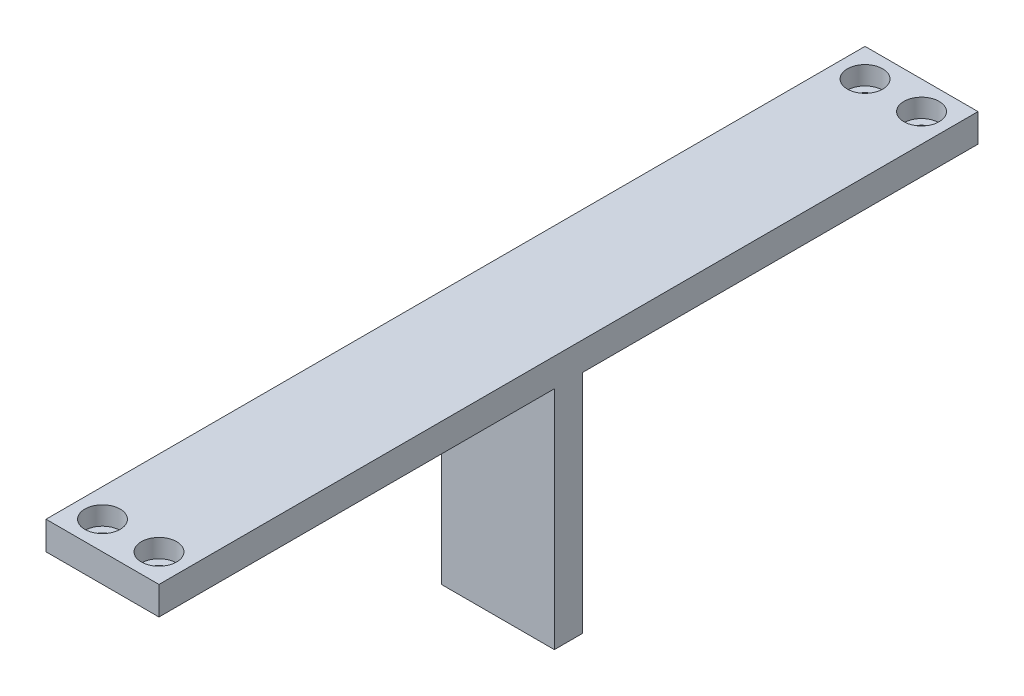
SolidWorks part; units mm, degrees
material "6061 Alloy"
ref_plane "Front Plane" through (0, 0, 0) normal (0, 0, 1) x (1, 0, 0)
ref_plane "Top Plane" through (0, 0, 0) normal (0, 1, 0) x (1, 0, 0)
ref_plane "Right Plane" through (0, 0, 0) normal (1, 0, 0) x (0, 0, -1)
sketch "Sketch1" plane through (0, 0, 0) normal (0, 1, 0) x (1, 0, 0)
  line L1 (-12.7, -92.075) -> (12.7, -92.075)
  line L2 (-12.7, -92.075) -> (-12.7, 92.075)
  line L3 (-12.7, 92.075) -> (12.7, 92.075)
  line L4 (12.7, -92.075) -> (12.7, 92.075)
  line L5 (-12.7, -92.075) -> (12.7, 92.075) construction
  line L6 (-12.7, 92.075) -> (12.7, -92.075) construction
  point P0 (0, 0)
  dimension "D1" = 184.15
  dimension "D2" = 25.4
extrude "Boss-Extrude1" add sketch "Sketch1" along normal blind 6.35
sketch "Sketch2" plane through (0, 0, 0) normal (0, -1, 0) x (-1, 0, 0)
  line L0 (-12.7, -92.075) -> (-12.7, 92.075) construction
  line L1 (12.7, 3.175) -> (-12.7, 3.175)
  line L2 (12.7, 3.175) -> (12.7, -3.175)
  line L3 (12.7, -3.175) -> (-12.7, -3.175)
  line L4 (-12.7, 3.175) -> (-12.7, -3.175)
  line L5 (12.7, 3.175) -> (-12.7, -3.175) construction
  line L6 (12.7, -3.175) -> (-12.7, 3.175) construction
  point P0 (0, 0)
  dimension "D1" = 6.35
extrude "Boss-Extrude2" add sketch "Sketch2" along normal blind 50.8
hole_wizard "CBORE for #8 Socket Head Cap Screw1" positions "Sketch4" profile "Sketch5" counterbore size "#8" standard "ANSI Inch" end condition up to next
sketch "Sketch4" plane through (0, 6.35, 0) normal (0, 1, 0) x (1, 0, 0)
  line L0 (-12.7, 92.075) -> (-12.7, -92.075) construction
  line L1 (-12.7, -92.075) -> (12.7, -92.075) construction
  line L2 (12.7, 92.075) -> (-12.7, 92.075) construction
  point P0 (-6.35, -85.725)
  point P2 (6.35, -85.725)
  point P4 (6.35, 85.725)
  point P6 (-6.35, 85.725)
  dimension "D1" = 6.35
  dimension "D2" = 6.35
  dimension "D3" = 6.35
  dimension "D4" = 19.05
  dimension "D5" = 6.35
  dimension "D6" = 19.05
  dimension "D7" = 6.35
  dimension "D8" = 6.35
sketch "Sketch5" plane through (-6.35, 6.35, 85.725) normal (1, 0, 0) x (0, 0, 1)
  line L0 (0, 0) -> (0, 6.35)
  line L1 (0, 6.35) -> (2.1526, 6.35)
  line L3 (2.1526, 6.35) -> (2.1527, 4.1656)
  line L4 (2.1527, 4.1656) -> (3.9687, 4.1656)
  line L5 (3.9687, 4.1656) -> (3.9687, 0)
  line L7 (3.9687, 0) -> (0, 0)
  line L11 (0, -6.35) -> (0, 107.95) construction
  dimension "Thru Hole Dia." = 4.3053
  dimension "Thru Hole Depth" = 6.35
  dimension "C'Bore Dia." = 7.9375
  dimension "C'Bore Depth" = 4.1656
